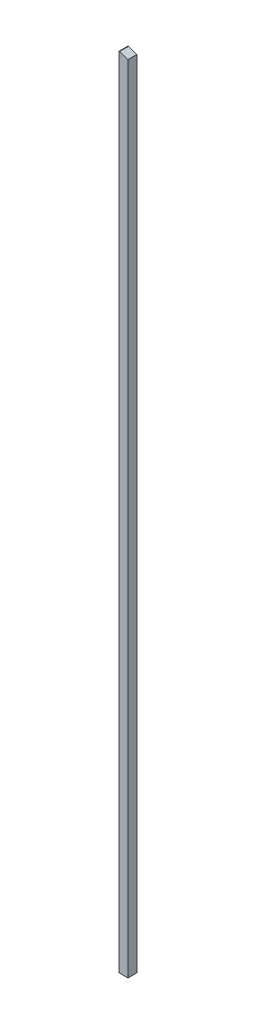
SolidWorks part; units mm, degrees
ref_plane "Front Plane" through (0, 0, 0) normal (0, 0, 1) x (1, 0, 0)
ref_plane "Top Plane" through (0, 0, 0) normal (0, 1, 0) x (1, 0, 0)
ref_plane "Right Plane" through (0, 0, 0) normal (1, 0, 0) x (0, 0, -1)
sketch "Sketch1" plane through (0, 0, 0) normal (0, 1, 0) x (1, 0, 0)
  line L1 (0, 0) -> (25.4, 0)
  line L2 (0, 0) -> (0, 25.4)
  line L3 (0, 25.4) -> (25.4, 25.4)
  line L4 (25.4, 0) -> (25.4, 25.4)
  dimension "D1" = 25.4
  dimension "D2" = 25.4
extrude "Boss-Extrude1" add sketch "Sketch1" along normal blind 2286
chamfer "Chamfer1" distance 8.382 distance2 23.876 1 edges at (25.4, 2286, -12.7) first distance on face at (25.4, 1143, -12.7)
